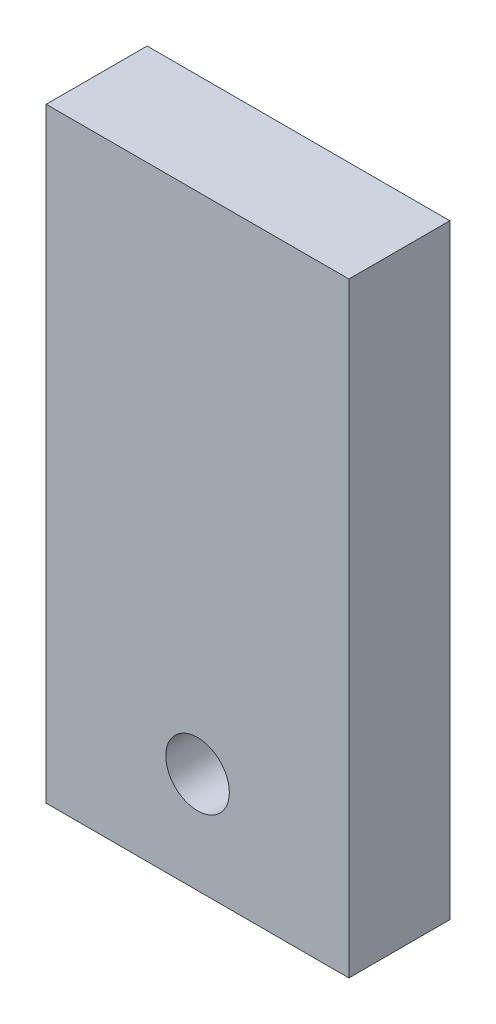
SolidWorks part; units mm, degrees
ref_plane "Front Plane" through (0, 0, 0) normal (0, 0, 1) x (1, 0, 0)
ref_plane "Top Plane" through (0, 0, 0) normal (0, 1, 0) x (1, 0, 0)
ref_plane "Right Plane" through (0, 0, 0) normal (1, 0, 0) x (0, 0, -1)
sketch "Sketch1" plane through (0, 0, 0) normal (0, 0, 1) x (1, 0, 0)
  line L0 (55, 0) -> (-55, 0) construction
  line L1 (-19.05, -38.1) -> (19.05, -38.1)
  line L2 (-19.05, -38.1) -> (-19.05, 38.1)
  line L3 (-19.05, 38.1) -> (19.05, 38.1)
  line L4 (19.05, -38.1) -> (19.05, 38.1)
  line L5 (-19.05, -38.1) -> (19.05, 38.1) construction
  line L6 (-19.05, 38.1) -> (19.05, -38.1) construction
  line L7 (-12.7, 38.1) -> (12.7, 38.1)
  line L8 (-12.7, 38.1) -> (-12.7, 44.45)
  line L9 (-12.7, 44.45) -> (12.7, 44.45)
  line L10 (12.7, 38.1) -> (12.7, 44.45)
  line L11 (-12.7, -44.45) -> (12.7, -44.45)
  line L12 (12.7, -38.1) -> (12.7, -44.45)
  line L13 (-12.7, -38.1) -> (12.7, -38.1)
  line L14 (-12.7, -38.1) -> (-12.7, -44.45)
  point P0 (0, 0)
  point P10 (0, 44.45)
  point P11 (0, 38.1)
  point P18 (0, -38.1)
  point P19 (0, -44.45)
  dimension "D1" = 38.1
  dimension "D2" = 76.2
  dimension "D3" = 25.4
  dimension "D4" = 6.35
extrude "Boss-Extrude1" add sketch "Sketch1" along normal blind 12.7 contours L1 L4 L3 L2 region at (0, 0, 0)
sketch "Sketch2" plane through (0, 0, 12.7) normal (0, 0, 1) x (1, 0, 0)
  line L8 (-19.05, -38.1) -> (19.05, -38.1) construction
  circle A1 centre (0, -25.4) radius 4
  dimension "D2" = 12.7
  dimension "D1" = 8
extrude "Cut-Extrude1" cut sketch "Sketch2" against normal through all
